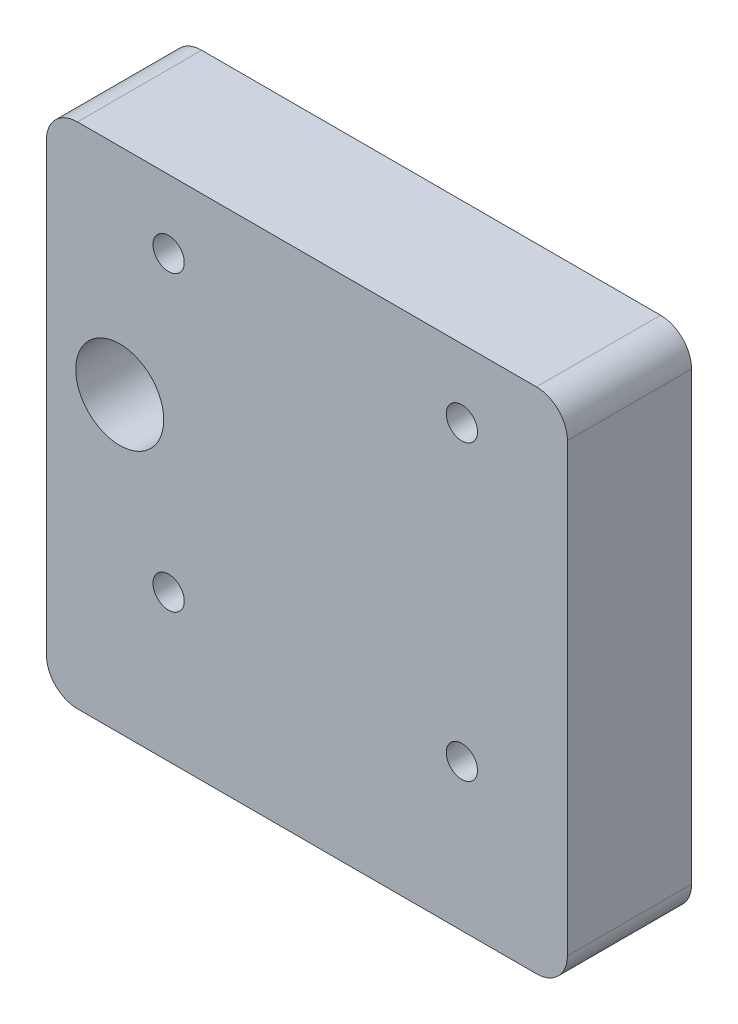
SolidWorks part; units mm, degrees
ref_plane "Front Plane" through (0, 0, 0) normal (0, 0, 1) x (1, 0, 0)
ref_plane "Top Plane" through (0, 0, 0) normal (0, 1, 0) x (1, 0, 0)
ref_plane "Right Plane" through (0, 0, 0) normal (1, 0, 0) x (0, 0, -1)
sketch "Sketch1" plane through (0, 0, 0) normal (0, 0, 1) x (1, 0, 0)
  line L0 (22.5, 0) -> (22.5, -44) construction
  line L1 (0, 0) -> (48.3, 0)
  line L2 (0, 0) -> (0, -44)
  line L3 (0, -44) -> (48.3, -44)
  line L4 (48.3, 0) -> (48.3, -44)
  line L5 (22.5, -22) -> (2.5, -22) construction
  circle A0 centre (7.5, -37) radius 1.6
  circle A20 centre (37.5, -37) radius 1.6
  circle A21 centre (37.5, -7) radius 1.6
  circle A22 centre (7.5, -7) radius 1.6
  circle A24 centre (0, 0) radius 2.5 construction
  circle A25 centre (2.5, -22) radius 4.5
  point P19 (22.5, -22)
  dimension "D3" = 3.2
  dimension "D10" = 9
  dimension "D1" = 48.3
  dimension "D2" = 44
  dimension "D4" = 7.5
  dimension "D5" = 7
  dimension "D8" = 30
  dimension "D9" = 30
  dimension "D12" = 22.5
  dimension "D11" = 20
  dimension "D6" = 2
  dimension "D7" = 2
extrude "Boss-Extrude1" add sketch "Sketch1" along normal blind 12.7 contours L4 L1 L2 L3 A0 region at (24.7224, -22, 0)
sketch "Sketch2" plane through (0, 0, 12.7) normal (0, 0, 1) x (1, 0, 0)
  line L1 (0, -44) -> (48.3, -44)
  line L2 (0, -44) -> (0, -52)
  line L3 (0, -52) -> (48.3, -52)
  line L4 (48.3, -44) -> (48.3, -52)
  line L5 (0, 0) -> (-5, 0)
  line L6 (0, 0) -> (0, -52)
  line L7 (0, -52) -> (-5, -52)
  line L8 (-5, 0) -> (-5, -52)
  line M12 (0, 0) -> (0, -18.2583)
  line M13 (0, -44) -> (48.3, -44)
  line M16 (0, -25.7417) -> (0, -44)
  dimension "D1" = 8
  dimension "D2" = 5
extrude "Boss-Extrude2" add sketch "Sketch2" against normal up to surface (12.7 mm away) contours L5 L8 L7 L2 L6 M16 M12 | L4 L2 L3 M13 region at (24.15, -48, 12.7) region at (-2.5, -26, 12.7) up to face at (17.2667, -22, 0)
extrude "Cut-Extrude3" cut sketch "Sketch1<5>" along normal through all contours L2 A25 | L2 A25 region at (3.1578, -22, 0) region at (-0.8175, -22, 0)
sketch "Sketch1<5>" plane through (0, 0, 0) normal (0, 0, 1) x (1, 0, 0) same geometry as "Sketch1"
fillet "Fillet1" radius 3.175 4 edges at (48.3, -52, 6.35) (48.3, 0, 6.35) (-5, 0, 6.35) (-5, -52, 6.35)
equation "\"D4@Sketch1\"=(\"D1@Sketch1\"-\"D9@Sketch1\")/2-1.65"
